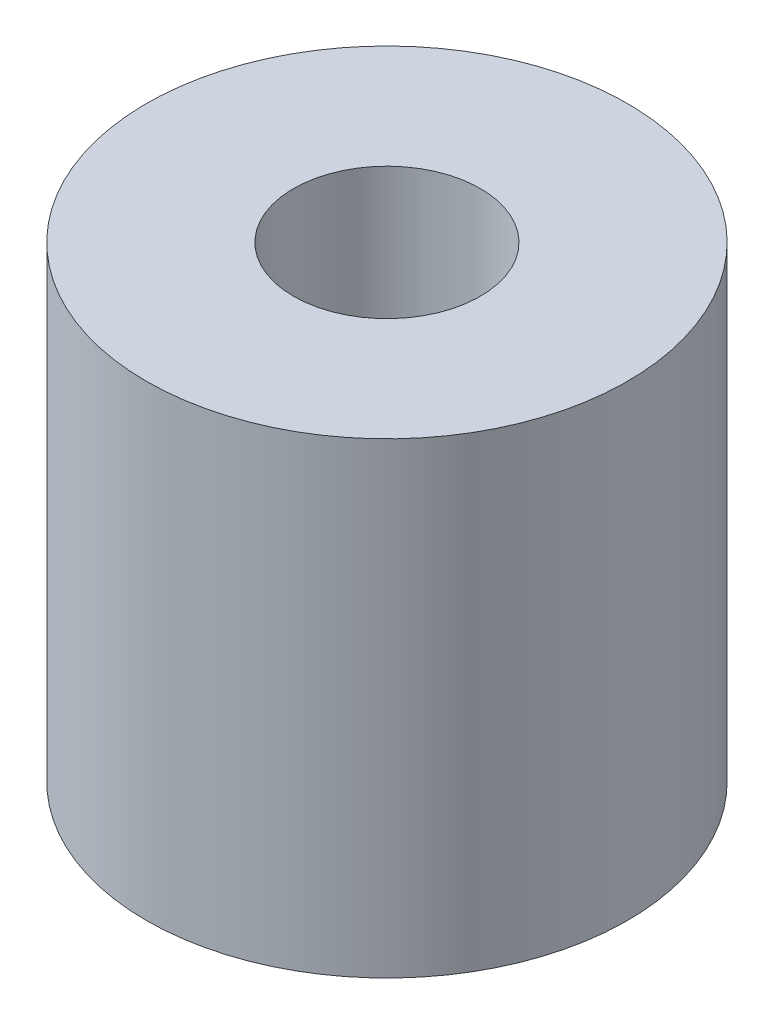
SolidWorks part; units mm, degrees
ref_plane "Front Plane" through (0, 0, 0) normal (0, 0, 1) x (1, 0, 0)
ref_plane "Top Plane" through (0, 0, 0) normal (0, 1, 0) x (1, 0, 0)
ref_plane "Right Plane" through (0, 0, 0) normal (1, 0, 0) x (0, 0, -1)
sketch "Sketch2" plane through (0, 0, 0) normal (0, 1, 0) x (1, 0, 0)
  line L1 (-6.4086, 0) -> (-3.2043, -5.55)
  line L2 (-3.2043, -5.55) -> (3.2043, -5.55)
  line L3 (3.2043, -5.55) -> (6.4086, 0)
  line L4 (6.4086, 0) -> (3.2043, 5.55)
  line L5 (3.2043, 5.55) -> (-3.2043, 5.55)
  line L6 (-3.2043, 5.55) -> (-6.4086, 0)
  circle A0 centre (0, 0) radius 3.3
  circle A1 centre (0, 0) radius 8.5
  circle A2 centre (0, 0) radius 5.55 construction
  dimension "D1" = 6.6
  dimension "D2" = 17
  dimension "D3" = 11.1
extrude "Boss-Extrude1" add sketch "Sketch2" along normal blind 2 contours L5 L6 L1 L2 L3 L4 A0 | A1 L6 L5 L4 L3 L2 L1 region at (-4.6596, 0, -2.6902) region at (-8.2596, 0, 0)
extrude "Boss-Extrude2" add sketch "Sketch2<4>" against normal blind 5.5 contours A1 L6 L5 L4 L3 L2 L1 region at (-8.2596, 0, 0)
sketch "Sketch2<4>" plane through (0, 0, 0) normal (0, 1, 0) x (1, 0, 0) same geometry as "Sketch2"
sketch "Sketch3" plane through (0, 2, 0) normal (0, 1, 0) x (1, 0, 0)
  circle A0 centre (0, 0) radius 8.5 construction
  circle A1 centre (0, 0) radius 3.3 construction
  circle A2 centre (0, 0) radius 8.5
  circle A3 centre (0, 0) radius 3.3
extrude "Boss-Extrude3" add sketch "Sketch3" along normal blind 9
